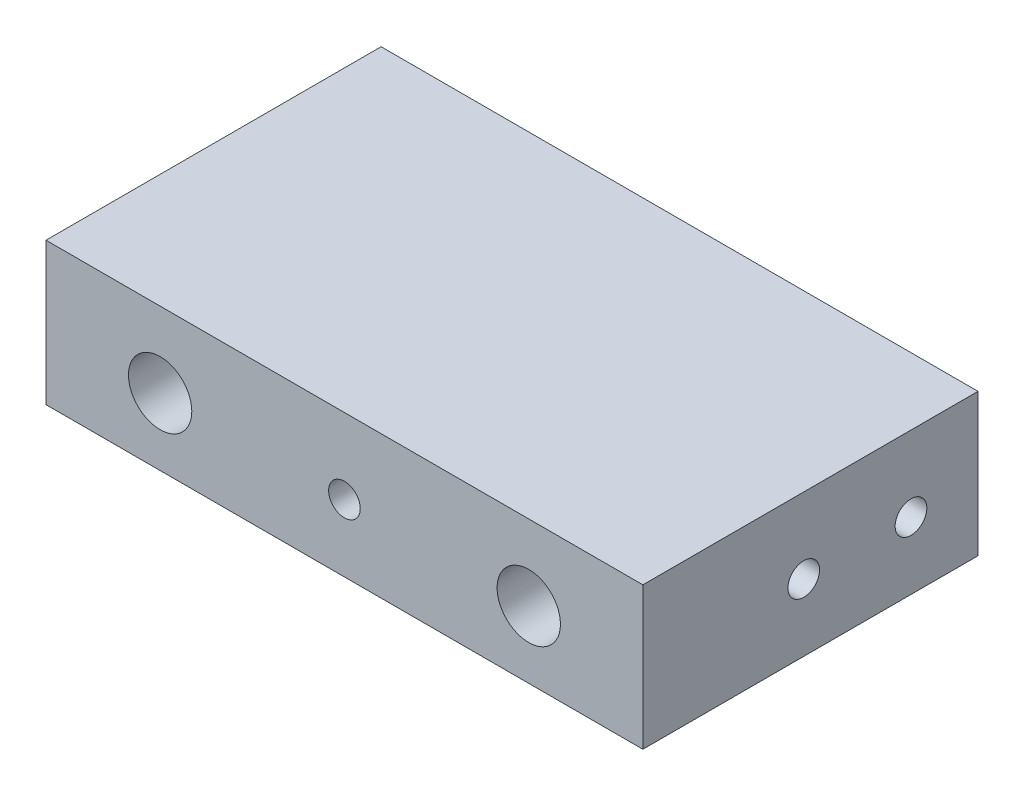
SolidWorks part; units mm, degrees
material "ABS"
ref_plane "X-Y Datum" through (0, 0, 0) normal (0, 0, 1) x (1, 0, 0)
ref_plane "X-Z Datum" through (0, 0, 0) normal (0, 1, 0) x (1, 0, 0)
ref_plane "Y-Z Datum" through (0, 0, 0) normal (1, 0, 0) x (0, 0, -1)
sketch "Sketch1" plane through (0, 0, 0) normal (0, 0, 1) x (1, 0, 0)
  line L1 (-28.275, 6.35) -> (28.275, 6.35)
  line L2 (-28.275, 6.35) -> (-28.275, -6.35)
  line L3 (-28.275, -6.35) -> (28.275, -6.35)
  line L4 (28.275, 6.35) -> (28.275, -6.35)
  line L5 (-28.275, 6.35) -> (28.275, -6.35) construction
  line L6 (-28.275, -6.35) -> (28.275, 6.35) construction
  point P0 (0, 0)
  dimension "D1" = 56.55
  dimension "D2" = 12.7
extrude "Boss-Extrude1" add sketch "Sketch1" along normal blind 31.75 contours L2 L3 L4 L1
sketch "Sketch2" plane through (0, 0, 31.75) normal (0, 0, 1) x (1, 0, 0)
  line L0 (-28.275, 0) -> (28.275, 0) construction
  line L1 (-28.275, 6.35) -> (-28.275, -6.35) construction
  line L2 (28.275, 6.35) -> (28.275, -6.35) construction
  line L3 (-17.4625, 0) -> (17.4625, 0) construction
  circle A0 centre (17.4625, 0) radius 3
  circle A1 centre (-17.4625, 0) radius 3
  circle A2 centre (0, 0) radius 1.5
  point P10 (0, 0)
  dimension "D1" = 6
  dimension "D3" = 3
  dimension "D2" = 34.925
extrude "Cut-Extrude1" cut sketch "Sketch2" against normal blind 10 contours A1 L0 L3 | L0 A1 L3 | L0 L3 A0 | L3 L0 A0 | A2 region at (17.4625, 0, 31.75) region at (-17.4625, 0, 31.75) region at (0, 0, 31.75)
sketch "Sketch3" plane through (-28.275, 0, 0) normal (-1, 0, 0) x (0, 0, 1)
  line L0 (31.75, 0) -> (0, 0) construction
  line L1 (31.75, 6.35) -> (31.75, -6.35) construction
  line L2 (0, 6.35) -> (0, -6.35) construction
  circle A0 centre (6.35, 0) radius 1.5
  circle A1 centre (16.51, 0) radius 1.5
  dimension "D1" = 3
  dimension "D2" = 10.16
  dimension "D3" = 6.35
extrude "Cut-Extrude2" cut sketch "Sketch3" against normal through all contours A0 L0 | L0 A0 | A1 L0 | L0 A1 region at (-28.275, -0.6366, 16.51) region at (-28.275, 0.6366, 16.51) region at (-28.275, -0.6366, 6.35) region at (-28.275, 0.6366, 6.35)
sketch "Sketch4" plane through (0, 6.35, 0) normal (0, 1, 0) x (1, 0, 0)
  line L4 (28.275, 0) -> (-28.275, 0)
  line L5 (-28.275, 0) -> (-28.275, -31.75)
  line L6 (-28.275, -31.75) -> (28.275, -31.75)
  line L7 (28.275, -31.75) -> (28.275, 0)
  line L8 (28.275, 0) -> (-28.275, 0)
  line L9 (-28.275, 0) -> (-28.275, -31.75)
  line L10 (-28.275, -31.75) -> (28.275, -31.75)
  line L11 (28.275, -31.75) -> (28.275, 0)
  dimension "D1" = 0
extrude "Boss-Extrude2" add sketch "Sketch4" along normal blind 0.7937
